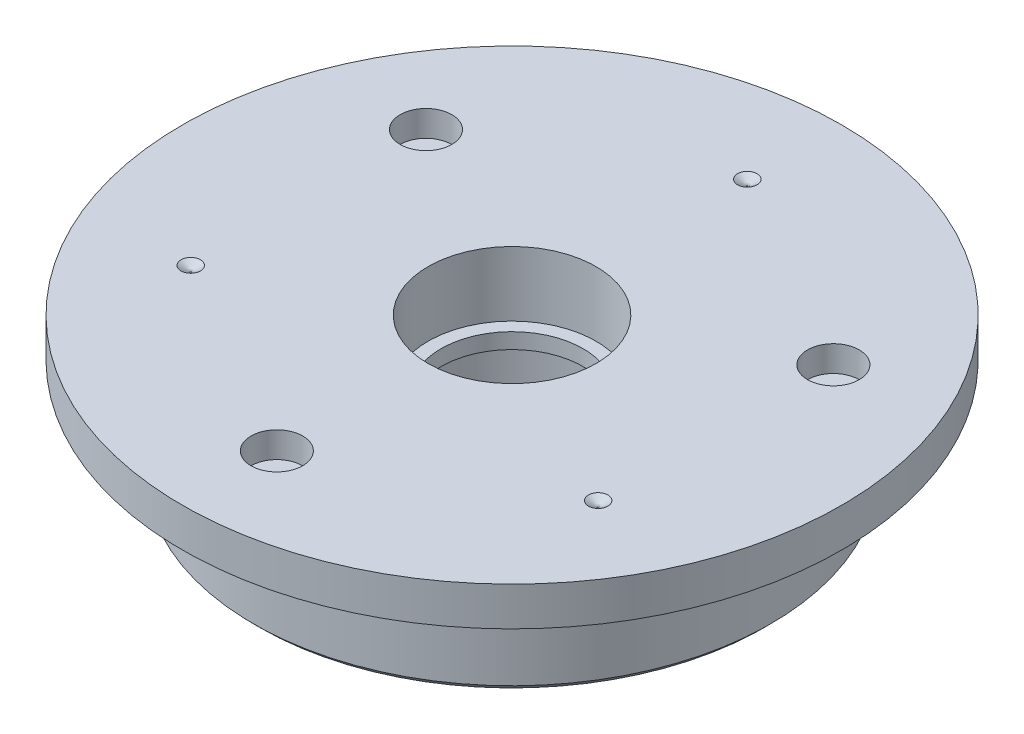
SolidWorks part; units mm, degrees
ref_plane "前视基准面" through (0, 0, 0) normal (0, 0, 1) x (1, 0, 0)
ref_plane "上视基准面" through (0, 0, 0) normal (0, 1, 0) x (1, 0, 0)
ref_plane "右视基准面" through (0, 0, 0) normal (1, 0, 0) x (0, 0, -1)
other "Configuration Table"
sketch "草图1" plane through (0, 0, 0) normal (0, 0, 1) x (1, 0, 0)
  line L0 (25.5, -16.8) -> (0, -16.8)
  line L1 (0, -16.8) -> (0, -19.8)
  line L2 (0, -19.8) -> (25.5, -19.8)
  line L3 (25.5, -19.8) -> (25.5, -16.8)
  line L4 (0, -16.8) -> (0, -19.8) construction
revolve "旋转1" add sketch "草图1" angle 360 about L4 reverse direction yes
sketch "草图2" plane through (0, -19.8, 0) normal (0, -1, 0) x (1, 0, 0)
  circle A0 centre (0, 0) radius 21.5
extrude "凸台-拉伸1" add sketch "草图2" along normal blind 0.8
sketch "草图3" plane through (0, -20.6, 0) normal (0, -1, 0) x (1, 0, 0)
  circle A0 centre (0, 0) radius 20
extrude "凸台-拉伸2" add sketch "草图3" along normal blind 7.4
ref_plane "基准面1" through (0, 0, 9.1) normal (0, 0, 1) x (1, 0, 0)
sketch "草图4" plane through (0, 0, 9.1) normal (0, 0, 1) x (1, 0, 0)
  line L0 (-15.0109, -16.8) -> (-15.7617, -16.8)
  line L1 (-15.7617, -16.8) -> (-15.7617, -17.2511)
  line L2 (-15.7617, -17.2511) -> (-15.0109, -16.8)
  line L3 (-15.7617, -16.8) -> (-15.7617, -17.2511) construction
revolve "切除-旋转1" cut sketch "草图4" angle 360 about L3 reverse direction yes
sketch "草图5" plane through (0, 0, 9.1) normal (0, 0, 1) x (1, 0, 0)
  line L0 (16.5124, -16.8) -> (15.7617, -16.8)
  line L1 (15.7617, -16.8) -> (15.7617, -17.2511)
  line L2 (15.7617, -17.2511) -> (16.5124, -16.8)
  line L3 (15.7617, -16.8) -> (15.7617, -17.2511) construction
revolve "切除-旋转2" cut sketch "草图5" angle 360 about L3 reverse direction yes
ref_plane "基准面2" through (0, 0, -18.2) normal (0, 0, 1) x (1, 0, 0)
sketch "草图6" plane through (0, 0, -18.2) normal (0, 0, 1) x (1, 0, 0)
  line L0 (0.7507, -16.8) -> (0, -16.8)
  line L1 (0, -16.8) -> (0, -17.2511)
  line L2 (0, -17.2511) -> (0.7507, -16.8)
  line L3 (0, -16.8) -> (0, -17.2511) construction
revolve "切除-旋转3" cut sketch "草图6" angle 360 about L3 reverse direction yes
ref_plane "基准面3" through (0, 0, 0) normal (0, 0, -1) x (-1, 0, 0)
sketch "草图7" plane through (0, 0, 0) normal (0, 0, -1) x (-1, 0, 0)
  line L0 (-9, -28) -> (0, -28)
  line L1 (0, -28) -> (0, -16.8)
  line L2 (0, -16.8) -> (-6.5, -16.8)
  line L3 (-6.5, -16.8) -> (-6.5, -21.8)
  line L4 (-6.5, -21.8) -> (-5.5, -21.8)
  line L5 (-5.5, -21.8) -> (-5.5, -23)
  line L6 (-5.5, -23) -> (-9, -23)
  line L7 (-9, -23) -> (-9, -28)
  line L8 (0, -28) -> (0, -16.8) construction
revolve "切除-旋转4" cut sketch "草图7" angle 360 about L8 reverse direction yes
hole_wizard "Ø3.0 (3) 直径孔1" positions "草图9" profile "草图8" hole size "Ø3.0" standard "ANSI Metric"
sketch "草图9" plane through (0, -28, 0) normal (0, -1, 0) x (-1, 0, 0)
  point P0 (6, 10.3923)
  point P1 (-6, -10.3923)
sketch "草图8" plane through (-6, -28, -10.3923) normal (1, 0, 0) x (0, 0, -1)
  line L0 (0, 0) -> (0, 3)
  line L1 (0, 3) -> (1.5, 3)
  line L2 (1.5, 3) -> (1.5, 0)
  line L5 (1.5, 0) -> (0, 0)
  line L10 (0, 3) -> (-1.5, 3) construction
  line L11 (0, -6.35) -> (0, 107.95) construction
  dimension "孔直径" = 3
  dimension "孔深度" = 3
  dimension "导头角度" = 180
hole_wizard "Ø3.3 (3.3) 直径孔1" positions "草图11" profile "草图10" hole size "Ø3.3" standard "ANSI Metric"
sketch "草图11" plane through (0, -28, 0) normal (0, -1, 0) x (-1, 0, 0)
  point P0 (10.3923, -6)
  point P1 (0, -12)
  point P2 (-10.3923, -6)
  point P3 (-10.3923, 6)
  point P4 (0, 12)
  point P5 (10.3923, 6)
sketch "草图10" plane through (-10.3923, -28, 6) normal (1, 0, 0) x (0, 0, -1)
  line L0 (0, 0) -> (0, 8.9914)
  line L1 (0, 8.9914) -> (1.65, 8)
  line L2 (1.65, 8) -> (1.65, 0)
  line L5 (1.65, 0) -> (0, 0)
  line L10 (0, 8.9914) -> (-1.65, 8) construction
  line L11 (0, -6.35) -> (0, 107.95) construction
  dimension "孔直径" = 3.3
  dimension "孔深度" = 8
  dimension "导头角度" = 118
hole_wizard "Ø4.0 (4) 直径孔1" positions "草图13" profile "草图12" hole size "Ø4.0" standard "ANSI Metric"
sketch "草图13" plane through (0, -16.8, 0) normal (0, 1, 0) x (1, 0, 0)
  point P0 (15.7617, 9.1)
  point P1 (0, -18.2)
  point P2 (-15.7617, 9.1)
sketch "草图12" plane through (15.7617, -16.8, -9.1) normal (1, 0, 0) x (0, 0, 1)
  line L0 (0, 0) -> (0, 2)
  line L1 (0, 2) -> (2, 2)
  line L2 (2, 2) -> (2, 0)
  line L5 (2, 0) -> (0, 0)
  line L10 (0, 2) -> (-2, 2) construction
  line L11 (0, -6.35) -> (0, 107.95) construction
  dimension "孔直径" = 4
  dimension "孔深度" = 2
  dimension "导头角度" = 180
chamfer "倒角1" distance 0.375 angle 45 6 edges at (0, -28, -13.65) (10.3923, -28, -7.65) (-10.3923, -28, 4.35) (-10.3923, -28, -7.65) (0, -28, 10.35) (10.3923, -28, 4.35)
chamfer "倒角2" distance 0.5 angle 45 1 edges at (0, -28, -20)
